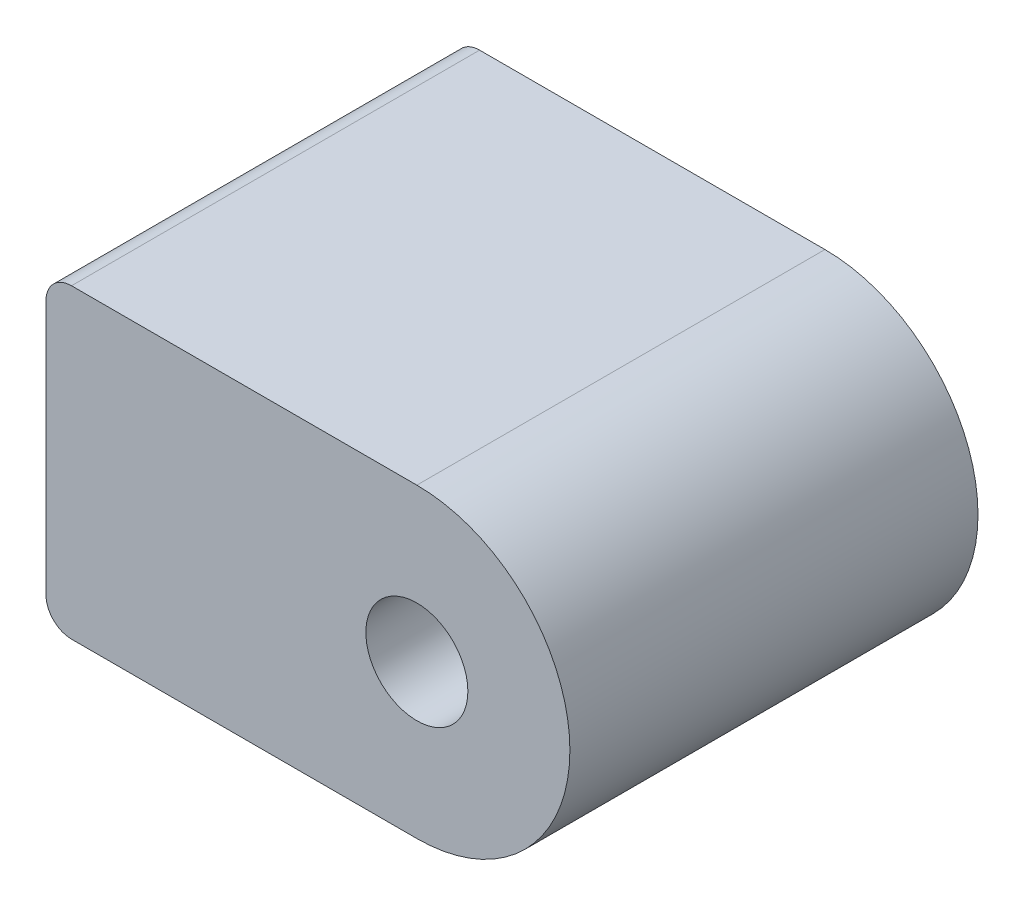
SolidWorks part; units mm, degrees
ref_plane "Front" through (0, 0, 0) normal (0, 0, 1) x (1, 0, 0)
ref_plane "Top" through (0, 0, 0) normal (0, 1, 0) x (1, 0, 0)
ref_plane "Right" through (0, 0, 0) normal (1, 0, 0) x (0, 0, -1)
sketch "Sketch1" plane through (0, 0, 0) normal (0, 0, 1) x (1, 0, 0)
  line L0 (-7.27, 3) -> (0, 3)
  line L1 (0, -3) -> (-7.27, -3)
  line L2 (-7.27, 3) -> (-7.27, -3)
  circle A0 centre (0, 0) radius 3
  circle A1 centre (0, 0) radius 1
  dimension "D1" = 6
  dimension "D3" = 2
  dimension "D2" = 7.27
extrude "Boss-Extrude1" add sketch "Sketch1" along normal blind 8 contours A0 A1 | A0 L0 L2 L1 region at (-4.7675, 0, 0) region at (2.0613, 2.0613, 0)
sketch "Sketch2" plane through (-7.27, 0, 0) normal (-1, 0, 0) x (0, 0, 1)
  line L5 (55, 0) -> (-55, 0) construction
  line L6 (8, 3) -> (0, 3) construction
  line L7 (8, 3) -> (0, 3)
  circle A0 centre (4, 0) radius 2.65
  point P4 (2.3359, 0)
  point P5 (4.2199, 0)
  point P8 (4, 3)
  dimension "D1" = 5.3
extrude "Cut-Extrude1" cut sketch "Sketch2" against normal blind 3.3 from offset 0.4 contours A0 region at (-7.27, 0, 4) offset against normal yes
fillet "Fillet2" radius 0.5 2 edges at (-7.27, -3, 4) (-7.27, 3, 4)
